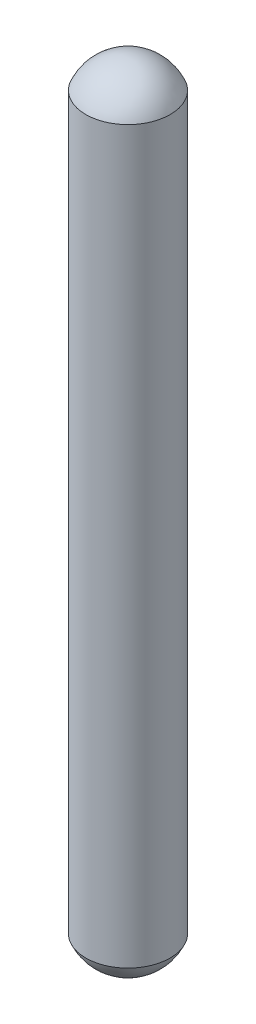
SolidWorks part; units mm, degrees
ref_plane "Front Plane" through (0, 0, 0) normal (0, 0, 1) x (1, 0, 0)
ref_plane "Top Plane" through (0, 0, 0) normal (0, 1, 0) x (1, 0, 0)
ref_plane "Right Plane" through (0, 0, 0) normal (1, 0, 0) x (0, 0, -1)
sketch "Sketch1" plane through (0, 0, 0) normal (0, 1, 0) x (1, 0, 0)
  circle A0 centre (0, 0) radius 3
extrude "Boss-Extrude1" add sketch "Sketch1" along normal blind 52
dome "Dome1" faces to dome 1 distance 2 reverse direction no elliptical dome no face at (0, 52, 3) parameters "D1"=2
dome "Dome2" faces to dome 1 distance 2 reverse direction no elliptical dome no face at (0, 0, 3) parameters "D1"=2
